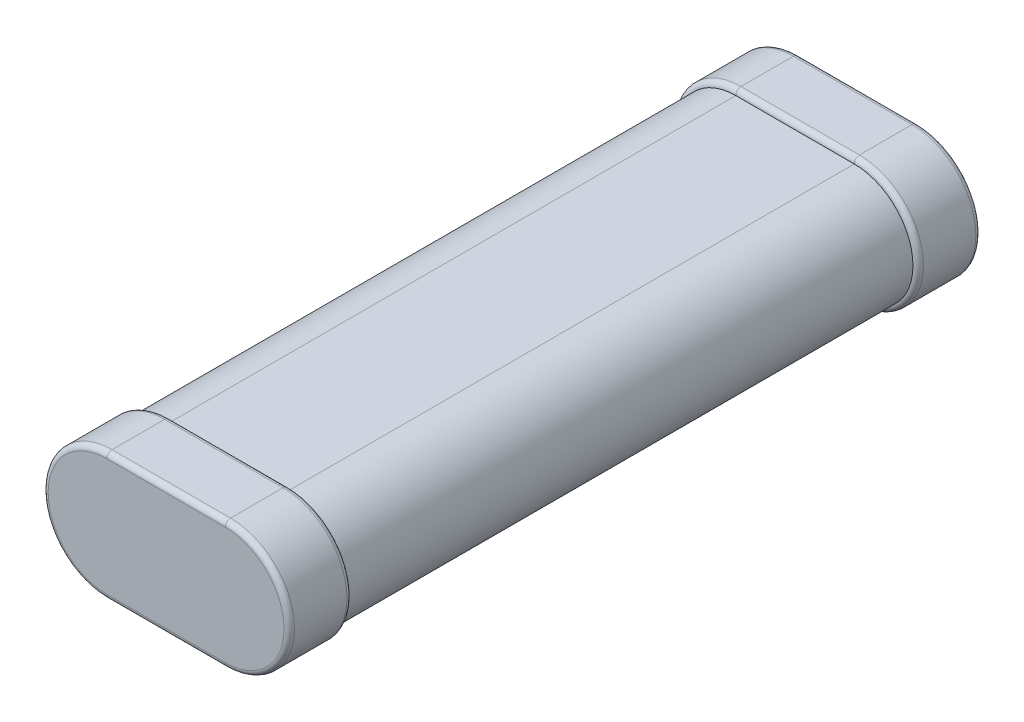
SolidWorks part; units mm, degrees
ref_plane "前视基准面" through (0, 0, 0) normal (0, 0, 1) x (1, 0, 0)
ref_plane "上视基准面" through (0, 0, 0) normal (0, 1, 0) x (1, 0, 0)
ref_plane "右视基准面" through (0, 0, 0) normal (1, 0, 0) x (0, 0, -1)
sketch "草图1" plane through (0, 0, 0) normal (0, 0, 1) x (1, 0, 0)
  line L0 (-23.5, 0) -> (-23.5, -15.7384) construction
  line L1 (23.5, 0) -> (23.5, -15.7384) construction
  line L2 (-11.3, 12.2) -> (11.3, 12.2)
  line L3 (-11.3, -12.2) -> (11.3, -12.2)
  line L4 (11.3, 0) -> (-11.3, 0) construction
  arc A0 (-11.3, 12.2) -> (-11.3, -12.2) centre (-11.3, 0) ccw
  arc A1 (11.3, -12.2) -> (11.3, 12.2) centre (11.3, 0) ccw
  dimension "D1" = 24.4
  dimension "D2" = 24.4
  dimension "D3" = 47
extrude "凸台-拉伸1" add sketch "草图1" along normal blind 132
ref_plane "基准面1" through (0, 0, 12) normal (0, 0, -1) x (-1, 0, 0)
sketch "草图2" plane through (0, 0, 12) normal (0, 0, -1) x (-1, 0, 0)
  line L0 (11.3, 11.2) -> (-11.3, 11.2)
  line L1 (-11.3, -11.2) -> (11.3, -11.2)
  line L2 (11.3, 12.2) -> (-11.3, 12.2)
  line L3 (-11.3, -12.2) -> (11.3, -12.2)
  line L4 (11.3, 12.2) -> (-11.3, 12.2)
  line L5 (-11.3, -12.2) -> (11.3, -12.2)
  arc A0 (-11.3, 11.2) -> (-11.3, -11.2) centre (-11.3, 0) ccw
  arc A1 (11.3, -11.2) -> (11.3, 11.2) centre (11.3, 0) ccw
  arc A2 (11.3, -12.2) -> (11.3, 12.2) centre (11.3, 0) ccw
  arc A3 (-11.3, 12.2) -> (-11.3, -12.2) centre (-11.3, 0) ccw
  arc A4 (11.3, -12.2) -> (11.3, 12.2) centre (11.3, 0) ccw
  arc A5 (-11.3, 12.2) -> (-11.3, -12.2) centre (-11.3, 0) ccw
  dimension "D1" = 0
  dimension "D2" = 1
extrude "切除-拉伸1" cut sketch "草图2" against normal blind 108
fillet "圆角1" radius 1 16 edges at (-23.5, 0, 12) (0, -12.2, 12) (23.5, 0, 12) (-23.5, 0, 120) (0, -12.2, 120) (23.5, 0, 120) (0, 12.2, 12) (0, 12.2, 120) (23.5, 0, 132) (0, -12.2, 132) (-23.5, 0, 132) (23.5, 0, 0) (0, -12.2, 0) (-23.5, 0, 0) (0, 12.2, 132) (0, 12.2, 0)
